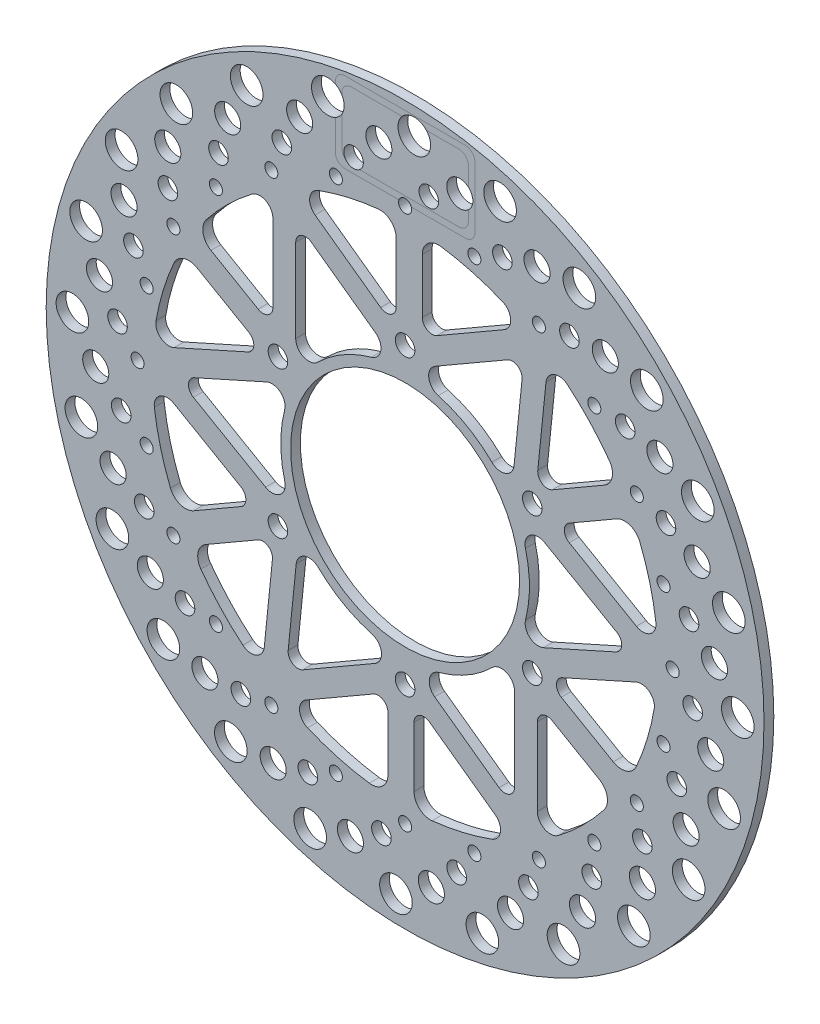
SolidWorks part; units mm, degrees
material "AISI 4130 Steel, normalized at 870C"
ref_plane "Front Plane" through (0, 0, 0) normal (0, 0, 1) x (1, 0, 0)
ref_plane "Top Plane" through (0, 0, 0) normal (0, 1, 0) x (1, 0, 0)
ref_plane "Right Plane" through (0, 0, 0) normal (1, 0, 0) x (0, 0, -1)
sketch "Sketch1" plane through (0, 0, 0) normal (0, 0, 1) x (1, 0, 0)
  circle A0 centre (0, 0) radius 110
  circle A1 centre (0, 45) radius 3
  circle A2 centre (38.9711, 22.5) radius 3
  circle A3 centre (38.9711, -22.5) radius 3
  circle A4 centre (0, -45) radius 3
  circle A5 centre (-38.9711, -22.5) radius 3
  circle A6 centre (-38.9711, 22.5) radius 3
  circle A7 centre (0, 0) radius 35.1
  point P18 (0, 0)
  dimension "D1" = 220
  dimension "D2" = 6
  dimension "D5" = 70.2
  dimension "D3" = 45
  dimension "D4" = 6
extrude "Boss-Extrude1" add sketch "Sketch1" along normal blind 3
sketch "Sketch2" plane through (0, 0, 3) normal (0, 0, 1) x (1, 0, 0)
  circle A2 centre (0, 0) radius 78 construction
  circle A3 centre (0, 0) radius 110 construction
  circle A4 centre (41.2098, 40.6578) radius 58.3732 construction
  circle A5 centre (29.0997, 97.761) radius 5
  circle A6 centre (16.762, 93.6647) radius 4
  circle A7 centre (7.2517, 88.137) radius 3
  circle A8 centre (0, 82) radius 2
  circle A9 centre (21.2232, 79.2059) radius 2
  circle A10 centre (29.8161, 83.2569) radius 3
  circle A11 centre (40.433, 86.1348) radius 4
  circle A12 centre (53.4106, 86.8983) radius 5
  circle A13 centre (41, 71.0141) radius 2
  circle A14 centre (50.3487, 72.703) radius 3
  circle A15 centre (61.3486, 72.735) radius 4
  circle A16 centre (74.0816, 70.1136) radius 5
  circle A17 centre (57.9828, 57.9828) radius 2
  circle A18 centre (67.45, 57.1945) radius 3
  circle A19 centre (78.0834, 54.3784) radius 4
  circle A20 centre (89.7041, 48.5508) radius 5
  circle A21 centre (71.0141, 41) radius 2
  circle A22 centre (79.9547, 37.7883) radius 3
  circle A23 centre (89.497, 32.3161) radius 4
  circle A24 centre (99.2133, 23.6794) radius 5
  circle A25 centre (79.2059, 21.2232) radius 2
  circle A26 centre (87.0107, 15.8069) radius 3
  circle A27 centre (94.8114, 8.0514) radius 4
  circle A28 centre (101.9614, -2.8058) radius 5
  circle A29 centre (82, 0) radius 2
  circle A30 centre (88.137, -7.2517) radius 3
  circle A31 centre (93.6647, -16.762) radius 4
  circle A32 centre (97.761, -29.0997) radius 5
  circle A33 centre (79.2059, -21.2232) radius 2
  circle A34 centre (83.2569, -29.8161) radius 3
  circle A35 centre (86.1348, -40.433) radius 4
  circle A36 centre (86.8983, -53.4106) radius 5
  circle A37 centre (71.0141, -41) radius 2
  circle A38 centre (72.703, -50.3487) radius 3
  circle A39 centre (72.735, -61.3486) radius 4
  circle A40 centre (70.1136, -74.0816) radius 5
  circle A41 centre (57.9828, -57.9828) radius 2
  circle A42 centre (57.1945, -67.45) radius 3
  circle A43 centre (54.3784, -78.0834) radius 4
  circle A44 centre (48.5508, -89.7041) radius 5
  circle A45 centre (41, -71.0141) radius 2
  circle A46 centre (37.7883, -79.9547) radius 3
  circle A47 centre (32.3161, -89.497) radius 4
  circle A48 centre (23.6794, -99.2133) radius 5
  circle A49 centre (21.2232, -79.2059) radius 2
  circle A50 centre (15.8069, -87.0107) radius 3
  circle A51 centre (8.0514, -94.8114) radius 4
  circle A52 centre (-2.8058, -101.9614) radius 5
  circle A53 centre (0, -82) radius 2
  circle A54 centre (-7.2517, -88.137) radius 3
  circle A55 centre (-16.762, -93.6647) radius 4
  circle A56 centre (-29.0997, -97.761) radius 5
  circle A57 centre (-21.2232, -79.2059) radius 2
  circle A58 centre (-29.8161, -83.2569) radius 3
  circle A59 centre (-40.433, -86.1348) radius 4
  circle A60 centre (-53.4106, -86.8983) radius 5
  circle A61 centre (-41, -71.0141) radius 2
  circle A62 centre (-50.3487, -72.703) radius 3
  circle A63 centre (-61.3486, -72.735) radius 4
  circle A64 centre (-74.0816, -70.1136) radius 5
  circle A65 centre (-57.9828, -57.9828) radius 2
  circle A66 centre (-67.45, -57.1945) radius 3
  circle A67 centre (-78.0834, -54.3784) radius 4
  circle A68 centre (-89.7041, -48.5508) radius 5
  circle A69 centre (-71.0141, -41) radius 2
  circle A70 centre (-79.9547, -37.7883) radius 3
  circle A71 centre (-89.497, -32.3161) radius 4
  circle A72 centre (-99.2133, -23.6794) radius 5
  circle A73 centre (-79.2059, -21.2232) radius 2
  circle A74 centre (-87.0107, -15.8069) radius 3
  circle A75 centre (-94.8114, -8.0514) radius 4
  circle A76 centre (-101.9614, 2.8058) radius 5
  circle A77 centre (-82, 0) radius 2
  circle A78 centre (-88.137, 7.2517) radius 3
  circle A79 centre (-93.6647, 16.762) radius 4
  circle A80 centre (-97.761, 29.0997) radius 5
  circle A81 centre (-79.2059, 21.2232) radius 2
  circle A82 centre (-83.2569, 29.8161) radius 3
  circle A83 centre (-86.1348, 40.433) radius 4
  circle A84 centre (-86.8983, 53.4106) radius 5
  circle A85 centre (-71.0141, 41) radius 2
  circle A86 centre (-72.703, 50.3487) radius 3
  circle A87 centre (-72.735, 61.3486) radius 4
  circle A88 centre (-70.1136, 74.0816) radius 5
  circle A89 centre (-57.9828, 57.9828) radius 2
  circle A90 centre (-57.1945, 67.45) radius 3
  circle A91 centre (-54.3784, 78.0834) radius 4
  circle A92 centre (-48.5508, 89.7041) radius 5
  circle A93 centre (-41, 71.0141) radius 2
  circle A94 centre (-37.7883, 79.9547) radius 3
  circle A95 centre (-32.3161, 89.497) radius 4
  circle A96 centre (-23.6794, 99.2133) radius 5
  circle A97 centre (-21.2232, 79.2059) radius 2
  circle A98 centre (-15.8069, 87.0107) radius 3
  circle A99 centre (-8.0514, 94.8114) radius 4
  circle A100 centre (2.8058, 101.9614) radius 5
  point P225 (0, 0)
  dimension "D1" = 32
  dimension "D2" = 10
  dimension "D3" = 8
  dimension "D4" = 6
  dimension "D5" = 4
  dimension "D6" = 82
  dimension "D7" = 9.5
  dimension "D8" = 11
  dimension "D9" = 13
  dimension "D10" = 102
  dimension "D11" = 24
extrude "Cut-Extrude1" cut sketch "Sketch2" against normal blind 10
sketch "Sketch3" plane through (0, 0, 3) normal (0, 0, 1) x (1, 0, 0)
  line L0 (-32.8138, 65.7565) -> (0, 42.0757) construction
  line L1 (0, 42.0757) -> (41.0163, 65.7565) construction
  line L2 (-28.7743, 58.0033) -> (-11.5835, 45.5971)
  line L3 (-27.5922, 65.7826) -> (-7.4871, 51.2733)
  line L4 (9.7685, 52.4398) -> (30.3588, 64.3276)
  line L5 (43.1733, 56.7869) -> (40.6605, 32.1207)
  line L8 (0, 42.0757) -> (0, 82) construction
  line L9 (5.2685, 55.0379) -> (5.2685, 71.7532)
  line L10 (-2.7315, 53.706) -> (-2.7315, 72.0866)
  line L11 (-2.7315, 42.0757) -> (-2.7315, 82) construction
  line L12 (5.2685, 42.0757) -> (5.2685, 82) construction
  line L13 (45.145, 29.2186) -> (61.063, 38.4088)
  line L14 (50.2984, 22.9563) -> (64.7744, 31.314)
  line L15 (50.2984, 17.7601) -> (70.8887, 5.8723)
  line L16 (70.7655, -8.9958) -> (48.1476, -19.1526)
  line L17 (47.8765, -24.4874) -> (63.7946, -33.6777)
  line L18 (45.0299, -32.0816) -> (59.5059, -40.4393)
  line L19 (40.5299, -34.6796) -> (40.5299, -58.4553)
  line L20 (27.5922, -65.7826) -> (7.4871, -51.2733)
  line L21 (2.7315, -53.706) -> (2.7315, -72.0866)
  line L22 (-5.2685, -55.0379) -> (-5.2685, -71.7532)
  line L23 (-9.7685, -52.4398) -> (-30.3588, -64.3276)
  line L24 (-43.1733, -56.7869) -> (-40.6605, -32.1207)
  line L25 (-45.145, -29.2186) -> (-61.063, -38.4088)
  line L26 (-50.2984, -22.9563) -> (-64.7744, -31.314)
  line L27 (-50.2984, -17.7601) -> (-70.8887, -5.8723)
  line L28 (-70.7655, 8.9958) -> (-48.1476, 19.1526)
  line L29 (-47.8765, 24.4874) -> (-63.7946, 33.6777)
  line L30 (-45.0299, 32.0816) -> (-59.5059, 40.4393)
  line L31 (-40.5299, 34.6796) -> (-40.5299, 58.4553)
  line L32 (-33.5299, 34.6796) -> (-33.5299, 55.5706)
  line L33 (-33.5299, 34.6796) -> (-33.5299, 58.4553) construction
  line L34 (-31.6886, 60.1064) -> (-11.5835, 45.5971) construction
  line L35 (-33.5299, 34.6796) -> (-33.5299, 30.0065)
  line L36 (-11.5835, 45.5971) -> (-9.0545, 43.772)
  line L37 (13.2685, 46.3776) -> (9.2215, 44.0411)
  line L38 (13.2685, 46.3776) -> (31.3606, 56.8231)
  line L39 (35.8451, 53.921) -> (33.6965, 32.8301)
  line L40 (33.6965, 32.8301) -> (33.3804, 29.7275)
  line L41 (46.7984, 11.698) -> (42.7514, 14.0345)
  line L42 (46.7984, 11.698) -> (64.8905, 1.2525)
  line L43 (64.6195, -4.0823) -> (45.28, -12.767)
  line L44 (45.28, -12.767) -> (42.435, -14.0446)
  line L45 (33.5299, -34.6796) -> (33.5299, -30.0065)
  line L46 (33.5299, -34.6796) -> (33.5299, -55.5706)
  line L47 (28.7743, -58.0033) -> (11.5835, -45.5971)
  line L48 (11.5835, -45.5971) -> (9.0545, -43.772)
  line L49 (-13.2685, -46.3776) -> (-9.2215, -44.0411)
  line L50 (-13.2685, -46.3776) -> (-31.3606, -56.8231)
  line L51 (-35.8451, -53.921) -> (-33.6965, -32.8301)
  line L52 (-33.6965, -32.8301) -> (-33.3804, -29.7275)
  line L53 (-46.7984, -11.698) -> (-42.7514, -14.0345)
  line L54 (-46.7984, -11.698) -> (-64.8905, -1.2525)
  line L55 (-64.6195, 4.0823) -> (-45.28, 12.767)
  line L56 (-45.28, 12.767) -> (-42.435, 14.0446)
  arc A0 (-8.2647, 77.0581) -> (-26.6256, 72.7827) centre (0, 0) ccw
  arc A3 (29.9025, 71.4818) -> (10.9768, 76.7028) centre (0, 0) ccw
  arc A4 (30.3588, 64.3276) -> (29.9025, 71.4818) centre (28.3588, 67.7917) ccw
  arc A5 (-27.5922, 65.7826) -> (-26.6256, 72.7827) centre (-25.2514, 69.0262) cw
  arc A6 (5.2685, 55.0379) -> (9.7685, 52.4398) centre (8.2685, 55.0379) ccw
  arc A7 (-7.4871, 51.2733) -> (-2.7315, 53.706) centre (-5.7315, 53.706) ccw
  arc A8 (5.2685, 71.7532) -> (10.9768, 76.7028) centre (10.2685, 71.7532) cw
  arc A9 (-2.7315, 72.0866) -> (-8.2647, 77.0581) centre (-7.7315, 72.0866) ccw
  arc A10 (40.6605, 32.1207) -> (45.145, 29.2186) centre (43.645, 31.8166) ccw
  arc A11 (61.063, 38.4088) -> (62.6019, 45.6865) centre (58.563, 42.739) ccw
  arc A12 (62.6019, 45.6865) -> (49.7189, 59.4498) centre (0, 0) ccw
  arc A13 (43.1733, 56.7869) -> (49.7189, 59.4498) centre (47.1527, 56.3815) cw
  arc A14 (64.7744, 31.314) -> (71.915, 28.8452) centre (67.2744, 26.9838) cw
  arc A15 (50.2984, 22.9563) -> (50.2984, 17.7601) centre (51.7984, 20.3582) ccw
  arc A16 (76.8563, 9.8446) -> (71.915, 28.8452) centre (0, 0) ccw
  arc A17 (70.8887, 5.8723) -> (76.8563, 9.8446) centre (72.8887, 9.3364) ccw
  arc A18 (48.1476, -19.1526) -> (47.8765, -24.4874) centre (49.3765, -21.8894) ccw
  arc A19 (63.7946, -33.6777) -> (70.8666, -31.3716) centre (66.2946, -29.3476) ccw
  arc A20 (70.8666, -31.3716) -> (76.3445, -13.3329) centre (0, 0) ccw
  arc A21 (70.7655, -8.9958) -> (76.3445, -13.3329) centre (72.4041, -12.6447) cw
  arc A22 (59.5059, -40.4393) -> (60.9382, -47.8576) centre (57.0059, -44.7694) cw
  arc A23 (45.0299, -32.0816) -> (40.5299, -34.6796) centre (43.5299, -34.6796) ccw
  arc A24 (46.9539, -61.6372) -> (60.9382, -47.8576) centre (0, 0) ccw
  arc A25 (40.5299, -58.4553) -> (46.9539, -61.6372) centre (44.5299, -58.4553) ccw
  arc A26 (7.4871, -51.2733) -> (2.7315, -53.706) centre (5.7315, -53.706) ccw
  arc A27 (2.7315, -72.0866) -> (8.2647, -77.0581) centre (7.7315, -72.0866) ccw
  arc A28 (8.2647, -77.0581) -> (26.6256, -72.7827) centre (0, 0) ccw
  arc A29 (27.5922, -65.7826) -> (26.6256, -72.7827) centre (25.2514, -69.0262) cw
  arc A30 (-5.2685, -71.7532) -> (-10.9768, -76.7028) centre (-10.2685, -71.7532) cw
  arc A31 (-5.2685, -55.0379) -> (-9.7685, -52.4398) centre (-8.2685, -55.0379) ccw
  arc A32 (-29.9025, -71.4818) -> (-10.9768, -76.7028) centre (0, 0) ccw
  arc A33 (-30.3588, -64.3276) -> (-29.9025, -71.4818) centre (-28.3588, -67.7917) ccw
  arc A34 (-40.6605, -32.1207) -> (-45.145, -29.2186) centre (-43.645, -31.8166) ccw
  arc A35 (-61.063, -38.4088) -> (-62.6019, -45.6865) centre (-58.563, -42.739) ccw
  arc A36 (-62.6019, -45.6865) -> (-49.7189, -59.4498) centre (0, 0) ccw
  arc A37 (-43.1733, -56.7869) -> (-49.7189, -59.4498) centre (-47.1527, -56.3815) cw
  arc A38 (-64.7744, -31.314) -> (-71.915, -28.8452) centre (-67.2744, -26.9838) cw
  arc A39 (-50.2984, -22.9563) -> (-50.2984, -17.7601) centre (-51.7984, -20.3582) ccw
  arc A40 (-76.8563, -9.8446) -> (-71.915, -28.8452) centre (0, 0) ccw
  arc A41 (-70.8887, -5.8723) -> (-76.8563, -9.8446) centre (-72.8887, -9.3364) ccw
  arc A42 (-48.1476, 19.1526) -> (-47.8765, 24.4874) centre (-49.3765, 21.8894) ccw
  arc A43 (-63.7946, 33.6777) -> (-70.8666, 31.3716) centre (-66.2946, 29.3476) ccw
  arc A44 (-70.8666, 31.3716) -> (-76.3445, 13.3329) centre (0, 0) ccw
  arc A45 (-70.7655, 8.9958) -> (-76.3445, 13.3329) centre (-72.4041, 12.6447) cw
  arc A46 (-59.5059, 40.4393) -> (-60.9382, 47.8576) centre (-57.0059, 44.7694) cw
  arc A47 (-45.0299, 32.0816) -> (-40.5299, 34.6796) centre (-43.5299, 34.6796) ccw
  arc A48 (-46.9539, 61.6372) -> (-60.9382, 47.8576) centre (0, 0) ccw
  arc A49 (-40.5299, 58.4553) -> (-46.9539, 61.6372) centre (-44.5299, 58.4553) ccw
  arc A51 (-9.0545, 43.772) -> (-10.3126, 36.6778) centre (-11.3953, 40.5285) cw
  circle A52 centre (0, 0) radius 38.1
  arc A53 (-10.3126, 36.6778) -> (-26.7242, 27.1556) centre (0, 0) ccw
  arc A54 (-33.5299, 30.0065) -> (-26.7242, 27.1556) centre (-29.5299, 30.0065) ccw
  arc A55 (-33.5299, 55.5706) -> (-28.7743, 58.0033) centre (-30.5299, 55.5706) cw
  arc A56 (26.6076, 27.2699) -> (10.1553, 36.7217) centre (0, 0) ccw
  arc A57 (9.2215, 44.0411) -> (10.1553, 36.7217) centre (11.2215, 40.5769) ccw
  arc A58 (33.3804, 29.7275) -> (26.6076, 27.2699) centre (29.401, 30.1329) cw
  arc A59 (31.3606, 56.8231) -> (35.8451, 53.921) centre (32.8606, 54.225) cw
  arc A60 (36.9202, -9.4079) -> (36.8795, 9.5661) centre (0, 0) ccw
  arc A61 (42.7514, 14.0345) -> (36.8795, 9.5661) centre (40.7514, 10.5704) ccw
  arc A62 (42.435, -14.0446) -> (36.9202, -9.4079) centre (40.7963, -10.3956) cw
  arc A63 (64.8905, 1.2525) -> (64.6195, -4.0823) centre (63.3905, -1.3456) cw
  arc A64 (10.3126, -36.6778) -> (26.7242, -27.1556) centre (0, 0) ccw
  arc A65 (33.5299, -30.0065) -> (26.7242, -27.1556) centre (29.5299, -30.0065) ccw
  arc A66 (9.0545, -43.772) -> (10.3126, -36.6778) centre (11.3953, -40.5285) cw
  arc A67 (33.5299, -55.5706) -> (28.7743, -58.0033) centre (30.5299, -55.5706) cw
  arc A68 (-26.6076, -27.2699) -> (-10.1553, -36.7217) centre (0, 0) ccw
  arc A69 (-9.2215, -44.0411) -> (-10.1553, -36.7217) centre (-11.2215, -40.5769) ccw
  arc A70 (-33.3804, -29.7275) -> (-26.6076, -27.2699) centre (-29.401, -30.1329) cw
  arc A71 (-31.3606, -56.8231) -> (-35.8451, -53.921) centre (-32.8606, -54.225) cw
  arc A72 (-36.9202, 9.4079) -> (-36.8795, -9.5661) centre (0, 0) ccw
  arc A73 (-42.7514, -14.0345) -> (-36.8795, -9.5661) centre (-40.7514, -10.5704) ccw
  arc A74 (-42.435, 14.0446) -> (-36.9202, 9.4079) centre (-40.7963, 10.3956) cw
  arc A75 (-64.8905, -1.2525) -> (-64.6195, 4.0823) centre (-63.3905, 1.3456) cw
  point P25 (36.9264, 68.1194)
  point P131 (0, 0)
  point P194 (0, 0)
  dimension "D1" = 155
  dimension "D7" = 4
  dimension "D4" = 3
  dimension "D8" = 5
  dimension "D11" = 4
  dimension "D12" = 3
  dimension "D2" = 7
  dimension "D3" = 7
  dimension "D5" = 8
  dimension "D10" = 3
  dimension "D9" = 6
  dimension "D13" = 6
extrude "Cut-Extrude2" cut sketch "Sketch3" against normal blind 13
sketch "Sketch5" plane through (0, 0, 0) normal (0, 0, -1) x (-1, 0, 0)
  line L0 (0.5379, 107.7948) -> (4.5155, 93.8062)
  line L1 (-102.3527, 33.822) -> (-87.8197, 33.2823)
  line L3 (-104.5795, -26.1367) -> (-90.0465, -26.6764)
  line L5 (-57.1743, 91.3844) -> (-53.1967, 77.3958)
  line L6 (102.6851, 32.7988) -> (90.6104, 24.6932)
  line L7 (69.2439, 82.6153) -> (57.1691, 74.5097)
  line L8 (62.925, -87.524) -> (51.4848, -78.545)
  line L9 (99.9693, -40.3253) -> (88.5291, -31.3463)
  line L10 (-63.7954, -86.8916) -> (-58.7911, -73.2367)
  line L11 (-7.4594, -107.5377) -> (-2.4551, -93.8828)
  arc A0 (-85.0945, 29.3074) -> (-87.034, -22.9147) centre (0, 0) ccw
  circle A1 centre (0, 0) radius 110
  arc A2 (-105.3368, 31.6883) -> (-107.3972, -23.7875) centre (0, 0) ccw
  circle A3 centre (0, 0) radius 110 construction
  circle A4 centre (0, 0) radius 90 construction
  circle A5 centre (0, 0) radius 110 construction
  arc A6 (-104.5795, -26.1367) -> (-107.3972, -23.7875) centre (-104.4682, -23.1387) cw
  arc A7 (-90.0465, -26.6764) -> (-87.034, -22.9147) centre (-89.9351, -23.6785) ccw
  arc A8 (-102.3527, 33.822) -> (-105.3368, 31.6883) centre (-102.464, 30.8241) ccw
  arc A9 (-87.8197, 33.2823) -> (-85.0945, 29.3074) centre (-87.931, 30.2843) cw
  arc A10 (1.5774, 89.9862) -> (-48.6881, 75.6932) centre (0, 0) ccw
  arc A11 (4.5155, 93.8062) -> (1.5774, 89.9862) centre (1.6299, 92.9857) cw
  arc A12 (-53.1967, 77.3958) -> (-48.6881, 75.6932) centre (-50.3111, 78.2164) ccw
  arc A13 (0.5379, 107.7948) -> (-2.4135, 109.9735) centre (-2.3477, 106.9742) ccw
  arc A14 (-2.4135, 109.9735) -> (-55.8108, 94.7901) centre (0, 0) ccw
  arc A15 (-57.1743, 91.3844) -> (-55.8108, 94.7901) centre (-54.2887, 92.2049) cw
  arc A16 (86.0694, 26.3071) -> (56.9431, 69.6956) centre (0, 0) ccw
  arc A17 (90.6104, 24.6932) -> (86.0694, 26.3071) centre (88.9383, 27.184) cw
  arc A18 (57.1691, 74.5097) -> (56.9431, 69.6956) centre (58.8412, 72.0188) ccw
  arc A19 (102.6851, 32.7988) -> (103.8452, 36.2791) centre (101.0131, 35.2896) ccw
  arc A20 (103.8452, 36.2791) -> (72.9042, 82.371) centre (0, 0) ccw
  arc A21 (69.2439, 82.6153) -> (72.9042, 82.371) centre (70.9159, 80.1245) cw
  arc A22 (51.6164, -73.7275) -> (83.8809, -32.619) centre (0, 0) ccw
  arc A23 (51.4848, -78.545) -> (51.6164, -73.7275) centre (53.337, -76.1851) cw
  arc A24 (88.5291, -31.3463) -> (83.8809, -32.619) centre (86.6769, -33.7063) ccw
  arc A25 (62.925, -87.524) -> (66.5934, -87.5518) centre (64.7772, -85.164) ccw
  arc A26 (66.5934, -87.5518) -> (100.8681, -43.882) centre (0, 0) ccw
  arc A27 (99.9693, -40.3253) -> (100.8681, -43.882) centre (98.1171, -42.6852) cw
  arc A28 (-54.1687, -71.8732) -> (-5.1019, -89.8553) centre (0, 0) ccw
  arc A29 (-58.7911, -73.2367) -> (-54.1687, -71.8732) centre (-55.9743, -74.269) cw
  arc A30 (-2.4551, -93.8828) -> (-5.1019, -89.8553) centre (-5.2719, -92.8505) ccw
  arc A31 (-63.7954, -86.8916) -> (-62.6882, -90.3891) centre (-60.9786, -87.9239) ccw
  arc A32 (-62.6882, -90.3891) -> (-10.5643, -109.4915) centre (0, 0) ccw
  arc A33 (-7.4594, -107.5377) -> (-10.5643, -109.4915) centre (-10.2762, -106.5054) cw
  point P19 (-104.6437, 33.9071)
  point P70 (0, 0)
  dimension "D4" = 3
  dimension "D3" = 60
  dimension "D1" = 0
  dimension "D2" = 20
  dimension "D5" = 5
split line "Split Line1" [suppressed]
sketch "Sketch6" plane through (0, 0, 0) normal (0, 0, -1) x (-1, 0, 0)
  line L0 (0, 0) -> (0, 125.5911) construction
  line L1 (-16.4078, 105.3137) -> (16.4078, 105.3137)
  line L2 (-18.4078, 107.3137) -> (18.4078, 107.3137)
  line L3 (-21.4078, 104.3137) -> (-21.4078, 85.6503)
  line L4 (-18.4078, 82.6503) -> (18.4078, 82.6503)
  line L5 (21.4078, 104.3137) -> (21.4078, 85.6503)
  line L6 (19.4078, 102.3137) -> (19.4078, 87.6503)
  line L7 (-16.4078, 84.6503) -> (16.4078, 84.6503)
  line L8 (-19.4078, 102.3137) -> (-19.4078, 87.6503)
  line L9 (19.4078, 105.3137) -> (19.4078, 84.6503) construction
  line L10 (-19.4078, 84.6503) -> (19.4078, 84.6503) construction
  line L11 (-21.4078, 82.6503) -> (21.4078, 82.6503) construction
  line L12 (21.4078, 107.3137) -> (21.4078, 82.6503) construction
  line L13 (-21.4078, 107.3137) -> (21.4078, 107.3137) construction
  line L14 (-19.4078, 105.3137) -> (19.4078, 105.3137) construction
  line L15 (-21.4078, 107.3137) -> (-21.4078, 82.6503) construction
  line L16 (-19.4078, 105.3137) -> (-19.4078, 84.6503) construction
  arc A0 (19.4078, 87.6503) -> (16.4078, 84.6503) centre (16.4078, 87.6503) cw
  arc A1 (18.4078, 82.6503) -> (21.4078, 85.6503) centre (18.4078, 85.6503) ccw
  arc A2 (18.4078, 107.3137) -> (21.4078, 104.3137) centre (18.4078, 104.3137) cw
  arc A3 (16.4078, 105.3137) -> (19.4078, 102.3137) centre (16.4078, 102.3137) cw
  arc A4 (-21.4078, 85.6503) -> (-18.4078, 82.6503) centre (-18.4078, 85.6503) ccw
  arc A5 (-16.4078, 84.6503) -> (-19.4078, 87.6503) centre (-16.4078, 87.6503) cw
  arc A6 (-16.4078, 105.3137) -> (-19.4078, 102.3137) centre (-16.4078, 102.3137) ccw
  arc A7 (-18.4078, 107.3137) -> (-21.4078, 104.3137) centre (-18.4078, 104.3137) ccw
  point P3 (0, 94.982)
  dimension "D2" = 3
  dimension "D1" = 2
split line "Split Line3"
split line "Split Line4"
sketch "Sketch6<2>" plane through (0, 0, 0) normal (0, 0, -1) x (-1, 0, 0) same geometry as "Sketch6"
